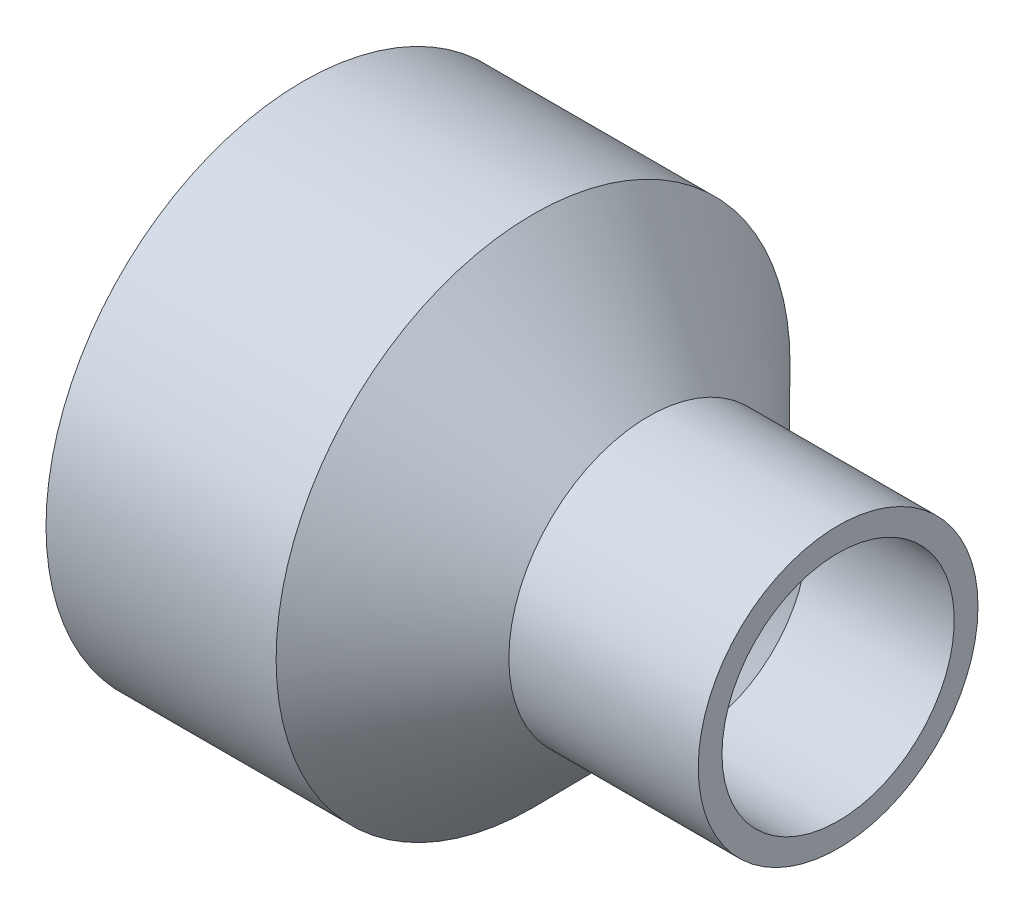
SolidWorks part; units mm, degrees
ref_plane "Front Plane" through (0, 0, 0) normal (0, 0, 1) x (1, 0, 0)
ref_plane "Top Plane" through (0, 0, 0) normal (0, 1, 0) x (1, 0, 0)
ref_plane "Right Plane" through (0, 0, 0) normal (1, 0, 0) x (0, 0, -1)
sketch "Sketch0" plane through (0, 0, 0) normal (0, 0, 1) x (1, 0, 0)
  line L0 (-69.85, 0) -> (31.75, 0) construction
  line L2 (-13.4938, 0) -> (31.75, 0) construction
  line L3 (-69.85, 0) -> (69.85, 0) construction
  line L4 (-69.85, 67.0719) -> (-69.85, -67.0719) construction
  line L5 (-13.4937, 57.0357) -> (-69.85, 57.3786) construction
  line L6 (-13.4937, 57.0357) -> (-13.4937, -57.0357) construction
  line L7 (-13.4937, -57.0357) -> (-69.85, -57.3786) construction
  line L8 (-69.85, 57.3786) -> (-69.85, -57.3786) construction
  line L9 (69.85, 30.3149) -> (69.85, -30.3149) construction
  line L10 (69.85, 36.5125) -> (69.85, -36.5125) construction
  line L11 (31.75, 24.6253) -> (31.75, -24.6253) construction
  line L12 (31.75, 30.0863) -> (31.75, -30.0863) construction
  line L13 (31.75, -30.0863) -> (69.85, -30.3149) construction
  line L14 (-13.4937, 48.5902) -> (-13.4937, -48.5902) construction
  line L15 (31.75, 30.0863) -> (69.85, 30.3149) construction
  dimension "N" = 45.2437
  dimension "M" = 134.1438
  dimension "OD A" = 114.7572
  dimension "OD B" = 114.0714
  dimension "ID" = 97.1804
  dimension "L" = 139.7
  dimension "ID2" = 49.2506
  dimension "OD B2" = 60.1726
  dimension "OD A2" = 60.6298
  dimension "M2" = 73.025
  dimension "C" = 56.3562
  dimension "C2" = 38.1
sketch "Sketch1" plane through (0, 0, 0) normal (0, 0, 1) x (1, 0, 0)
  line L0 (-69.85, 0) -> (31.75, 0) construction
  line L1 (-69.85, 0) -> (31.75, 0) construction
  line L2 (-13.4937, -57.0357) -> (15.8272, -27.3558)
  line L3 (0, -57.1693) -> (-6.8958, -50.3569) construction
  line L4 (-69.85, -67.0719) -> (-69.85, -57.3786)
  line L5 (-69.85, -57.3786) -> (-13.4937, -57.0357)
  line L6 (31.75, -27.3558) -> (28.9861, -27.3558) construction
  line L7 (28.9861, -27.3558) -> (31.75, -30.0863)
  line L8 (-9.7828, -67.0719) -> (20.4069, -36.5125)
  line L9 (-9.7828, -67.0719) -> (-69.85, -67.0719)
  line L10 (0, 0) -> (0, -57.1693) construction
  line L11 (28.9861, -27.3558) -> (15.8272, -27.3558)
  line L12 (31.75, -30.0863) -> (69.85, -30.3149)
  line L13 (69.85, -30.3149) -> (69.85, -36.5125)
  line L14 (69.85, -36.5125) -> (20.4069, -36.5125)
  line L15 (31.75, -24.6253) -> (31.75, -30.0863) construction
  dimension "D1" = 45
revolve "Revolve1" add sketch "Sketch1" angle 360 about L1
other "CPoint1" parameters "Diameter"=101.6, "StubLength"=152.4
ref_axis "Axis1" through (-23.4938, 0, 0) along (1, 0, 0)
other "CPoint2" parameters "Diameter"=50.8, "StubLength"=152.4
ref_axis "Axis2" through (41.75, 0, 0) along (-1, 0, 0)
other "RPoint1"
